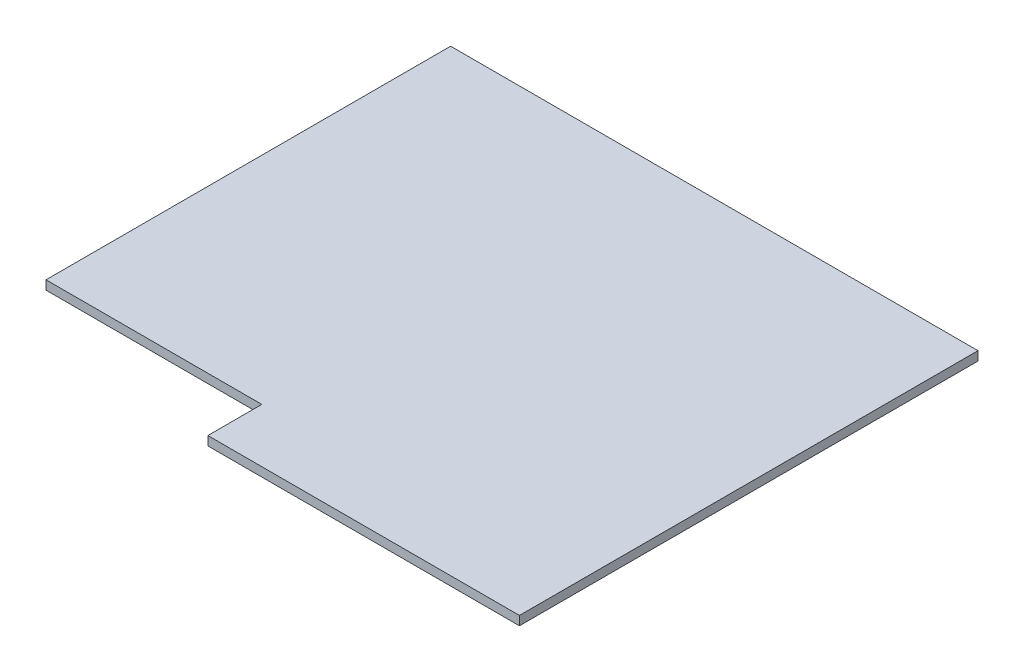
SolidWorks part; units mm, degrees
ref_plane "Front Plane" through (0, 0, 0) normal (0, 0, 1) x (1, 0, 0)
ref_plane "Top Plane" through (0, 0, 0) normal (0, 1, 0) x (1, 0, 0)
ref_plane "Right Plane" through (0, 0, 0) normal (1, 0, 0) x (0, 0, -1)
sketch "Sketch1" plane through (0, 0, 0) normal (0, 1, 0) x (1, 0, 0)
  line L0 (-86.635, 127.5) -> (-206.635, 127.5)
  line L1 (-86.635, -127.5) -> (86.635, -127.5)
  line L2 (-86.635, -127.5) -> (-86.635, 127.5)
  line L3 (-86.635, 127.5) -> (86.635, 127.5)
  line L4 (86.635, -127.5) -> (86.635, 127.5)
  line L5 (-86.635, -127.5) -> (86.635, 127.5) construction
  line L6 (-86.635, 127.5) -> (86.635, -127.5) construction
  line L7 (-206.635, 127.5) -> (-206.635, -97.5)
  line L8 (-206.635, -97.5) -> (-86.635, -97.5)
  point P0 (0, 0)
  dimension "D1" = 255
  dimension "D2" = 173.27
  dimension "D3" = 120
  dimension "D4" = 30
extrude "Boss-Extrude1" add sketch "Sketch1" along normal blind 5 contours L7 L8 L2 L0 | L1 L4 L3 L2 region at (-146.635, 0, -15) region at (0, 0, 0)
sketch "Sketch2" plane through (0, 5, 0) normal (0, 1, 0) x (1, 0, 0)
  line L0 (-86.635, -127.5) -> (86.635, -127.5) construction
  line L1 (86.635, -127.5) -> (86.635, 127.5) construction
  circle A0 centre (-27.5, -7.5) radius 20
  dimension "D1" = 40
  dimension "D2" = 120
  dimension "D3" = 114.135
